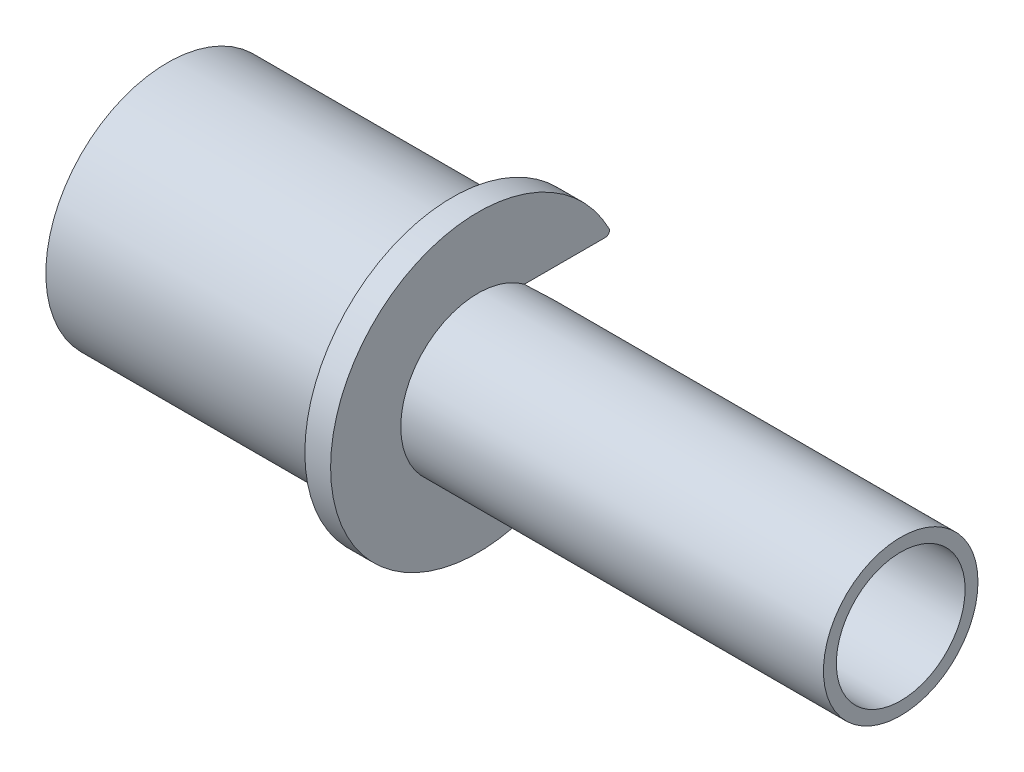
SolidWorks part; units mm, degrees
material "6061-T6 (SS)"
ref_plane "Front Plane" through (0, 0, 0) normal (0, 0, 1) x (1, 0, 0)
ref_plane "Top Plane" through (0, 0, 0) normal (0, 1, 0) x (1, 0, 0)
ref_plane "Right Plane" through (0, 0, 0) normal (1, 0, 0) x (0, 0, -1)
sketch "Sketch1" plane through (0, 0, 0) normal (0, 0, 1) x (1, 0, 0)
  line L0 (0, 0) -> (-16.6687, 0) construction
  line L1 (2.2375, 3.9687) -> (2.2375, 4.7625)
  line L2 (2.2375, 4.7625) -> (-23.8125, 4.7625)
  line L3 (-23.8125, 4.7625) -> (-23.8125, 9.0875)
  line L4 (-23.8125, 9.0875) -> (-25.4, 9.0875)
  line L5 (-25.4, 9.0875) -> (-25.4, 7.5)
  line L6 (-25.4, 7.5) -> (-42.95, 7.5)
  line L7 (-42.95, 7.5) -> (-42.95, 3.9687)
  line L8 (-42.95, 3.9687) -> (2.2375, 3.9687)
  line L9 (-25.4, -15.27) -> (-25.4, 15.27) construction
  line L10 (-57.15, -5.5562) -> (-57.15, 5.5563) construction
  line L14 (2.2375, -11.375) -> (2.2375, 11.375) construction
  dimension "D1" = 7.9375
  dimension "D4" = 15
  dimension "D3" = 9.525
  dimension "D2" = 1.5875
  dimension "D5" = 1.5875
  dimension "D6" = 14.2
revolve "Revolve1" add sketch "Sketch1" angle 360 about L0
sketch "Sketch2" plane through (2.2375, 0, 0) normal (1, 0, 0) x (0, 0, -1)
  line L0 (1.3441, 3.7342) -> (8.2848, 3.7342)
  line L1 (8.2848, -3.7342) -> (1.3441, -3.7342)
  line L2 (0, 0) -> (14.3216, 0) construction
  circle A0 centre (0, 0) radius 3.9687 construction
  circle A1 centre (0, 0) radius 9.0875 construction
  arc A2 (1.3441, 3.7342) -> (1.3441, -3.7342) centre (0, 0) cw
  arc A3 (8.2848, 3.7342) -> (8.2848, -3.7342) centre (0, 0) cw
  arc A4 (3.6742, 3.7342) -> (3.6742, -3.7342) centre (0, 0) cw construction
  circle A5 centre (5.2387, 0) radius 1.27 construction
  circle A6 centre (4.623, 2.4642) radius 1.27 construction
  circle A7 centre (4.623, -2.4642) radius 1.27 construction
  dimension "D1" = 1.27
  dimension "D2" = 2.54
extrude "Cut-Extrude1" [suppressed] cut sketch "Sketch2" against normal through all both
sketch "Sketch3" plane through (0, 0, 0) normal (0, 0, 1) x (1, 0, 0)
  line L0 (-42.95, 3.81) -> (-42.95, -3.81)
  line L1 (-42.95, 7.5) -> (-42.95, -7.5) construction
  line L2 (-42.95, -3.81) -> (-23.8125, -3.81)
  line L4 (-23.8125, 3.81) -> (-42.95, 3.81)
  line L5 (-20.6375, -0.635) -> (-20.6375, 0.635)
  line L6 (-20.6375, 0) -> (0, 0) construction
  line L8 (-23.8125, -9.0875) -> (-23.8125, 9.0875) construction
  arc A1 (-23.8125, -3.81) -> (-20.6375, -0.635) centre (-23.8125, -0.635) ccw
  arc A2 (-20.6375, 0.635) -> (-23.8125, 3.81) centre (-23.8125, 0.635) ccw
  dimension "D1" = 7.62
  dimension "D2" = 3.175
extrude "Cut-Extrude2" cut sketch "Sketch3" against normal up to next
fillet "Fillet1" radius 0.254 4 edges at (-24.6062, 3.81, -8.2502) (-24.6062, -3.81, -8.2502) (-34.175, -3.81, -6.4602) (-34.175, 3.81, -6.4602)
equation "\"bearing1\"=0.273438"
equation "\"D1@Sketch1\"=5/16"
equation "\"D4@Sketch1\"=15mm"
